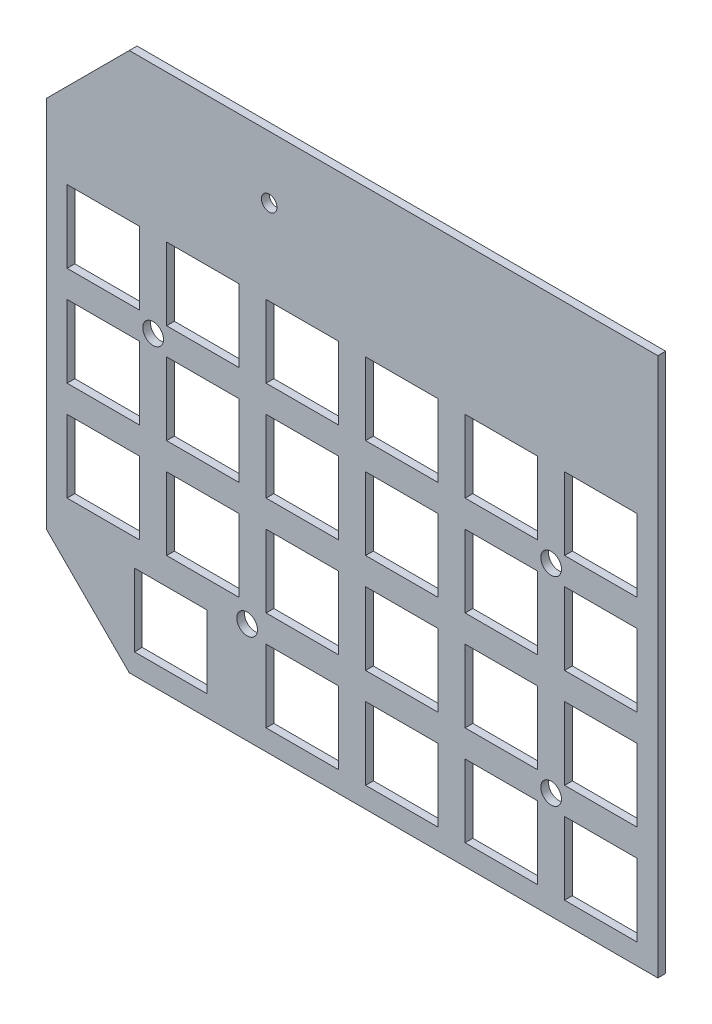
SolidWorks part; units mm, degrees
ref_plane "Plan de face" through (0, 0, 0) normal (0, 0, 1) x (1, 0, 0)
ref_plane "Plan de dessus" through (0, 0, 0) normal (0, 1, 0) x (1, 0, 0)
ref_plane "Plan de droite" through (0, 0, 0) normal (1, 0, 0) x (0, 0, -1)
sketch "Esquisse1" plane through (0, 0, 0) normal (0, 0, 1) x (1, 0, 0)
  line L0 (0, -85) -> (16, -101)
  line L4 (118, 3) -> (118, -101)
  line L5 (16, 3) -> (0, -13)
  line L7 (118, 3) -> (16, 3)
  line L8 (0, -13) -> (0, -85)
  line L9 (16, -101) -> (118, -101)
  dimension "D1" = 104
  dimension "D2" = 118
  dimension "D3" = 16
  dimension "D4" = 16
  dimension "D5" = 16
  dimension "D6" = 16
extrude "Boss.-Extru.1" add sketch "Esquisse1" along normal blind 1.5
sketch "Esquisse3" plane through (0, 0, 0) normal (0, 0, -1) x (-1, 0, 0)
  line L0 (-94.8, -25.4) -> (-94.8, -39.4)
  line L1 (-114, -25.4) -> (-100, -25.4)
  line L2 (-114, -25.4) -> (-114, -39.4)
  line L3 (-114, -39.4) -> (-100, -39.4)
  line L4 (-100, -25.4) -> (-100, -39.4)
  line L5 (-107, -39.4) -> (-107, -25.4) construction
  line L6 (-114, -32.4) -> (-100, -32.4) construction
  line L7 (-94.8, -25.4) -> (-80.8, -25.4)
  line L8 (-80.8, -25.4) -> (-80.8, -39.4)
  line L9 (-94.8, -39.4) -> (-80.8, -39.4)
  line L10 (-75.6, -25.4) -> (-75.6, -39.4)
  line L11 (-75.6, -25.4) -> (-61.6, -25.4)
  line L12 (-61.6, -25.4) -> (-61.6, -39.4)
  line L13 (-75.6, -39.4) -> (-61.6, -39.4)
  line L14 (-56.4, -25.4) -> (-56.4, -39.4)
  line L15 (-56.4, -25.4) -> (-42.4, -25.4)
  line L16 (-42.4, -25.4) -> (-42.4, -39.4)
  line L17 (-56.4, -39.4) -> (-42.4, -39.4)
  line L18 (-37.2, -25.4) -> (-37.2, -39.4)
  line L19 (-37.2, -25.4) -> (-23.2, -25.4)
  line L20 (-23.2, -25.4) -> (-23.2, -39.4)
  line L21 (-37.2, -39.4) -> (-23.2, -39.4)
  line L22 (-18, -25.4) -> (-18, -39.4)
  line L23 (-18, -25.4) -> (-4, -25.4)
  line L24 (-4, -25.4) -> (-4, -39.4)
  line L25 (-18, -39.4) -> (-4, -39.4)
  line L26 (-94.8, -44.6) -> (-94.8, -58.6)
  line L27 (-94.8, -44.6) -> (-80.8, -44.6)
  line L28 (-80.8, -44.6) -> (-80.8, -58.6)
  line L29 (-94.8, -58.6) -> (-80.8, -58.6)
  line L30 (-75.6, -44.6) -> (-75.6, -58.6)
  line L31 (-75.6, -44.6) -> (-61.6, -44.6)
  line L32 (-61.6, -44.6) -> (-61.6, -58.6)
  line L33 (-75.6, -58.6) -> (-61.6, -58.6)
  line L34 (-56.4, -44.6) -> (-56.4, -58.6)
  line L35 (-56.4, -44.6) -> (-42.4, -44.6)
  line L36 (-42.4, -44.6) -> (-42.4, -58.6)
  line L37 (-56.4, -58.6) -> (-42.4, -58.6)
  line L38 (-37.2, -44.6) -> (-37.2, -58.6)
  line L39 (-37.2, -44.6) -> (-23.2, -44.6)
  line L40 (-23.2, -44.6) -> (-23.2, -58.6)
  line L41 (-37.2, -58.6) -> (-23.2, -58.6)
  line L42 (-18, -44.6) -> (-18, -58.6)
  line L43 (-18, -44.6) -> (-4, -44.6)
  line L44 (-4, -44.6) -> (-4, -58.6)
  line L45 (-18, -58.6) -> (-4, -58.6)
  line L46 (-94.8, -63.8) -> (-94.8, -77.8)
  line L47 (-94.8, -63.8) -> (-80.8, -63.8)
  line L48 (-80.8, -63.8) -> (-80.8, -77.8)
  line L49 (-94.8, -77.8) -> (-80.8, -77.8)
  line L50 (-75.6, -63.8) -> (-75.6, -77.8)
  line L51 (-75.6, -63.8) -> (-61.6, -63.8)
  line L52 (-61.6, -63.8) -> (-61.6, -77.8)
  line L53 (-75.6, -77.8) -> (-61.6, -77.8)
  line L54 (-56.4, -63.8) -> (-56.4, -77.8)
  line L55 (-56.4, -63.8) -> (-42.4, -63.8)
  line L56 (-42.4, -63.8) -> (-42.4, -77.8)
  line L57 (-56.4, -77.8) -> (-42.4, -77.8)
  line L58 (-37.2, -63.8) -> (-37.2, -77.8)
  line L59 (-37.2, -63.8) -> (-23.2, -63.8)
  line L60 (-23.2, -63.8) -> (-23.2, -77.8)
  line L61 (-37.2, -77.8) -> (-23.2, -77.8)
  line L62 (-18, -63.8) -> (-18, -77.8)
  line L63 (-18, -63.8) -> (-4, -63.8)
  line L64 (-4, -63.8) -> (-4, -77.8)
  line L65 (-18, -77.8) -> (-4, -77.8)
  line L66 (-94.8, -83) -> (-94.8, -97)
  line L67 (-94.8, -83) -> (-80.8, -83)
  line L68 (-80.8, -83) -> (-80.8, -97)
  line L69 (-94.8, -97) -> (-80.8, -97)
  line L70 (-75.6, -83) -> (-75.6, -97)
  line L71 (-75.6, -83) -> (-61.6, -83)
  line L72 (-61.6, -83) -> (-61.6, -97)
  line L73 (-75.6, -97) -> (-61.6, -97)
  line L74 (-56.4, -83) -> (-56.4, -97)
  line L75 (-56.4, -83) -> (-42.4, -83)
  line L76 (-42.4, -83) -> (-42.4, -97)
  line L77 (-56.4, -97) -> (-42.4, -97)
  line L86 (-114, -44.6) -> (-114, -58.6)
  line L87 (-114, -44.6) -> (-100, -44.6)
  line L88 (-100, -44.6) -> (-100, -58.6)
  line L89 (-114, -58.6) -> (-100, -58.6)
  line L90 (-114, -63.8) -> (-114, -77.8)
  line L91 (-114, -63.8) -> (-100, -63.8)
  line L92 (-100, -63.8) -> (-100, -77.8)
  line L93 (-114, -77.8) -> (-100, -77.8)
  line L94 (-114, -83) -> (-114, -97)
  line L95 (-114, -83) -> (-100, -83)
  line L96 (-100, -83) -> (-100, -97)
  line L97 (-114, -97) -> (-100, -97)
  line L98 (-4, -83) -> (-4, -97) [skipped]
  line L99 (-18, -97) -> (-4, -97) [skipped]
  line L100 (-18, -83) -> (-18, -97) [skipped]
  line L101 (-18, -83) -> (-4, -83) [skipped]
  line L102 (-94.8, -83) -> (-100, -77.8) construction
  line L103 (-118, -101) -> (-118, 3) construction
  line L104 (-16, -101) -> (-118, -101) construction
  line L107 (-37.2, -83) -> (-23.2, -83) [skipped]
  line L108 (-23.2, -83) -> (-23.2, -97) [skipped]
  line L109 (-37.2, -83) -> (-37.2, -97) [skipped]
  line L110 (-37.2, -97) -> (-23.2, -97) [skipped]
  line L111 (0, -13) -> (0, -85) construction
  line L112 (-31, -83) -> (-17, -83)
  line L113 (-31, -83) -> (-31, -97)
  line L114 (-31, -97) -> (-17, -97)
  line L115 (-17, -83) -> (-17, -97)
  line L116 (-24, -97) -> (-24, -83) construction
  line L117 (-31, -90) -> (-17, -90) construction
  line L118 (-100, -39.4) -> (-94.8, -44.6) construction
  line L119 (-23.2, -39.4) -> (-18, -44.6) construction
  line L120 (-42.4, -77.8) -> (-35.0788, -85.1212) construction
  line L122 (-118, 3) -> (-16, 3) construction
  circle A0 centre (-97.4, -42) radius 2
  circle A1 centre (-20.6, -42) radius 2
  circle A2 centre (-38.7394, -81.4606) radius 2
  circle A3 centre (-97.4, -80.4) radius 2
  circle A5 centre (-43, -9) radius 1.5
  point P0 (-107, -32.4)
  point P84 (-24, -90)
  dimension "D7" = 43
  dimension "D8" = 12
  dimension "D1" = 14
  dimension "D2" = 14
  dimension "D5" = 4
  dimension "D6" = 4
  dimension "D9" = 5.2
  dimension "D10" = 14
  dimension "D11" = 14
  dimension "D12" = 17
  dimension "D13" = 5.2
  dimension "D3" = 6
  dimension "D4" = 4
extrude "Enlèv. mat.-Extru.2" cut sketch "Esquisse3" against normal blind 10
